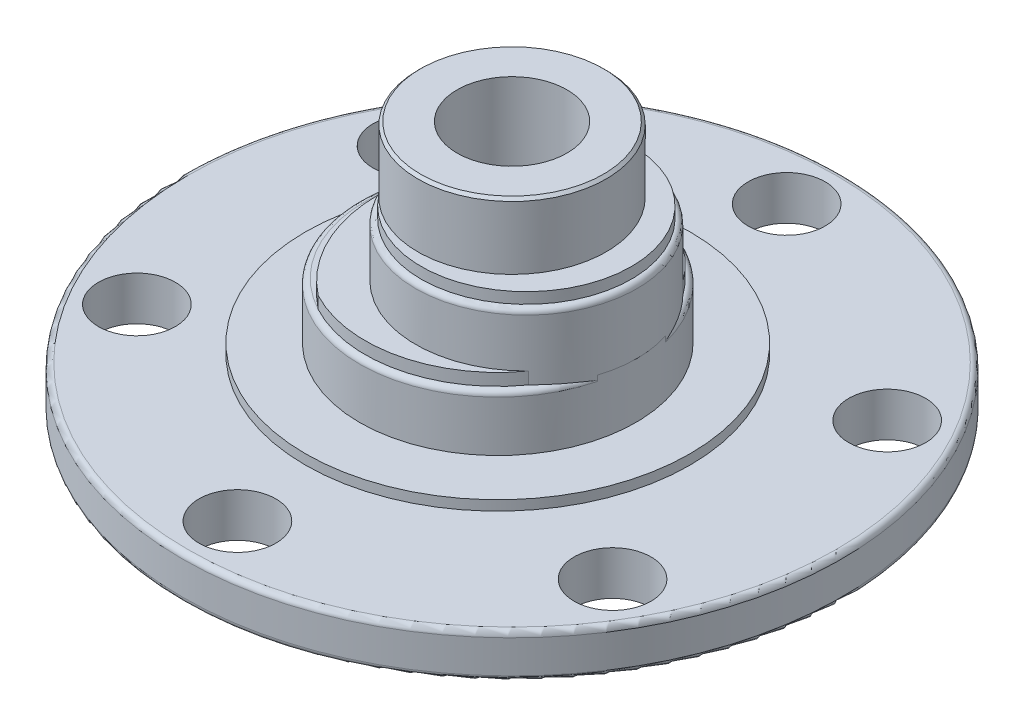
SolidWorks part; units mm, degrees
material "6061-T6 (SS)"
ref_plane "Front Plane" through (0, 0, 0) normal (0, 0, 1) x (1, 0, 0)
ref_plane "Top Plane" through (0, 0, 0) normal (0, 1, 0) x (1, 0, 0)
ref_plane "Right Plane" through (0, 0, 0) normal (1, 0, 0) x (0, 0, -1)
sketch "Sketch1" plane through (0, 0, 0) normal (0, 1, 0) x (1, 0, 0)
  circle A0 centre (0, 0) radius 25 construction
  circle A1 centre (0, 0) radius 30
  circle A2 centre (0, 25) radius 2.05
  circle A3 centre (21.6506, 12.5) radius 2.05
  circle A4 centre (21.6506, -12.5) radius 2.05
  circle A5 centre (0, -25) radius 2.05
  circle A6 centre (-21.6506, -12.5) radius 2.05
  circle A7 centre (-21.6506, 12.5) radius 2.05
  point P18 (0, 0)
  dimension "D1" = 50
  dimension "D2" = 60
  dimension "D3" = 4.1
  dimension "D4" = 6
extrude "Boss-Extrude1" add sketch "Sketch1" along normal blind 4
sketch "Sketch2" plane through (0, 4, 0) normal (0, 1, 0) x (1, 0, 0)
  circle A0 centre (-1.3, 0) radius 12.575
  point P0 (0, 0)
  point P1 (-1.3, 0)
  dimension "D2" = 25.15
  dimension "D1" = 1.3
extrude "Boss-Extrude2" add sketch "Sketch2" along normal blind 6
sketch "Sketch3" plane through (0, 10, 0) normal (0, 1, 0) x (1, 0, 0)
  circle A0 centre (1.3, 0) radius 10.075
  point P0 (1.3, 0)
  dimension "D2" = 20.15
  dimension "D1" = 1.3
extrude "Boss-Extrude3" add sketch "Sketch3" along normal blind 6
fillet "Fillet1" radius 0.5 4 edges at (1.3, 16, 10.075) (-13.875, 10, 0) (0, 0, 30) (0, 4, 30)
sketch "Sketch4" plane through (0, 4, 0) normal (0, 1, 0) x (1, 0, 0)
  circle A0 centre (0, 25) radius 3.5
  circle A1 centre (21.6506, 12.5) radius 3.5
  circle A2 centre (21.6506, -12.5) radius 3.5
  circle A3 centre (0, -25) radius 3.5
  circle A4 centre (-21.6506, -12.5) radius 3.5
  circle A5 centre (-21.6506, 12.5) radius 3.5
  point P16 (0, 0)
  dimension "D1" = 7
  dimension "D2" = 6
extrude "Cut-Extrude1" cut sketch "Sketch4" against normal blind 4
sketch "Sketch5" plane through (0, 16, 0) normal (0, 1, 0) x (1, 0, 0)
  circle A0 centre (0, 0) radius 8.575
  dimension "D1" = 17.15
extrude "Boss-Extrude4" add sketch "Sketch5" along normal blind 7
sketch "Sketch6" plane through (0, 4, 0) normal (0, 1, 0) x (1, 0, 0)
  circle A0 centre (-1.3, 0) radius 12.575 construction
  circle A1 centre (-1.3, 0) radius 12.575
  circle A2 centre (-1.3, 0) radius 17.5
  dimension "D1" = 35
extrude "Boss-Extrude5" add sketch "Sketch6" along normal blind 0.9
sketch "Sketch7" plane through (0, 10, 0) normal (0, 1, 0) x (1, 0, 0)
  circle A0 centre (1.3, 0) radius 10.075 construction
  circle A1 centre (1.3, 0) radius 10.075
  arc A3 (8.5192, 7.0277) -> (8.5192, -7.0277) centre (-1.3, 0) ccw construction
  arc A4 (8.5192, 7.0277) -> (-7.0085, 10.6404) centre (-1.3, 0) ccw
  arc A5 (-7.0085, 10.6404) -> (-7.0085, -10.6404) centre (1.3, 0) ccw
  arc A6 (-7.0085, -10.6404) -> (8.5192, -7.0277) centre (-1.3, 0) ccw
  arc M2 (8.5192, -7.0277) -> (8.5192, 7.0277) centre (1.3, 0) cw
  arc M3 (8.5192, 7.0277) -> (8.5192, -7.0277) centre (-1.3, 0) ccw
  dimension "D1" = 13.5
extrude "Boss-Extrude6" add sketch "Sketch7" along normal blind 1.1 contours A5 M3 M2 region at (-9.0932, 10, 0)
chamfer "Chamfer1" distance 0.25 angle 45 1 edges at (0, 23, 8.575)
sketch "Sketch8" plane through (0, 16, 0) normal (0, 1, 0) x (1, 0, 0)
  circle A0 centre (0, 0) radius 8.575 construction
  arc A1 (-6.3308, -5.7838) -> (-6.3308, 5.7838) centre (1.3, 0) ccw construction
  circle A2 centre (0, 0) radius 8.575
  arc A3 (-6.3308, -5.7838) -> (-6.3308, 5.7838) centre (1.3, 0) ccw
  arc M1 (-6.3308, -5.7838) -> (-6.3308, 5.7838) centre (1.3, 0) ccw
  arc M2 (-6.3308, 5.7838) -> (-6.3308, -5.7838) centre (0, 0) cw
extrude "Boss-Extrude7" add sketch "Sketch8" along normal blind 1 contours M2 M1 region at (3.1951, 16, -8.2343)
sketch "Sketch9" plane through (0, 23, 0) normal (0, 1, 0) x (1, 0, 0)
  circle A0 centre (0, 0) radius 5
  dimension "D1" = 10
extrude "Cut-Extrude2" cut sketch "Sketch9" against normal up to next
sketch "Sketch10" plane through (0, 0, 0) normal (0, -1, 0) x (1, 0, 0)
  circle A0 centre (0, 0) radius 10
  dimension "D1" = 20
extrude "Cut-Extrude3" cut sketch "Sketch10" against normal blind 7
